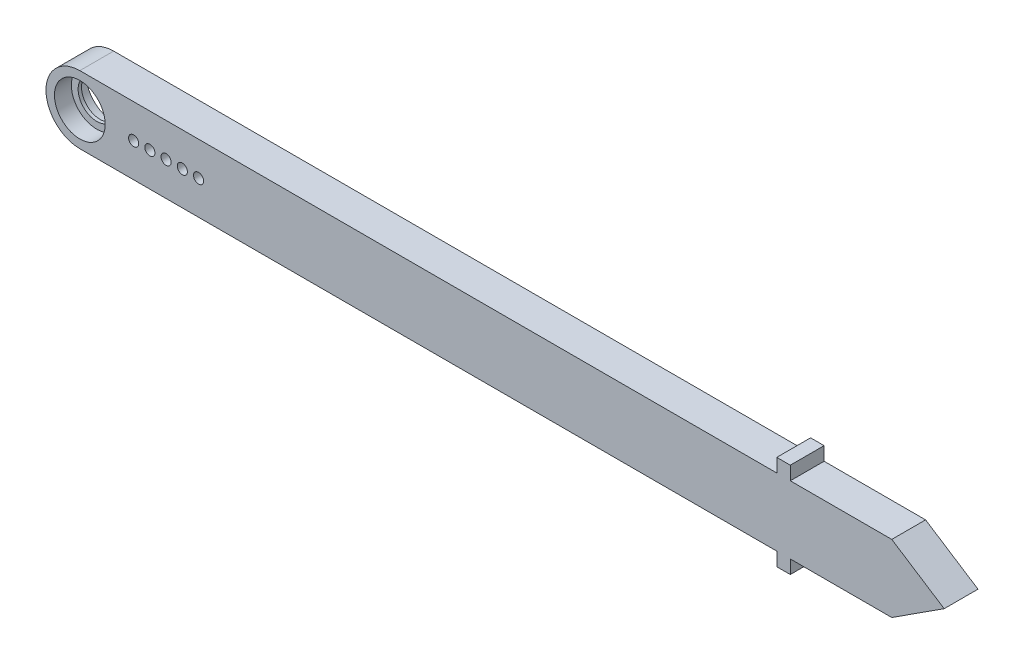
SolidWorks part; units mm, degrees
ref_plane "Front Plane" through (0, 0, 0) normal (0, 0, 1) x (1, 0, 0)
ref_plane "Top Plane" through (0, 0, 0) normal (0, 1, 0) x (1, 0, 0)
ref_plane "Right Plane" through (0, 0, 0) normal (1, 0, 0) x (0, 0, -1)
sketch "Sketch1" plane through (0, 0, 0) normal (0, 0, 1) x (1, 0, 0)
  line L0 (0, 0) -> (120, 0) construction
  line L1 (120, 5) -> (120, -5)
  line L2 (0, 5) -> (120, 5)
  line L3 (0, -5) -> (120, -5)
  circle A0 centre (0, 0) radius 3.75
  circle A1 centre (1.2272, 0) radius 0.1309
  arc A2 (0, 5) -> (0, -5) centre (0, 0) ccw
  dimension "D1" = 7.5
  dimension "D2" = 120
  dimension "D3" = 10
extrude "Boss-Extrude1" add sketch "Sketch1" along normal blind 5 contours L2 A2 L3 A0 region at (60.1767, 0, 0)
sketch "Sketch3" plane through (0, 0, 0) normal (0, 0, -1) x (-1, 0, 0)
  line L0 (-18.4, 0) -> (4.1, 0) construction
  line L3 (-16.1297, 2.7494) -> (0, 4.1)
  line L4 (-16.1297, -2.7494) -> (0, -4.1)
  arc A4 (0, -4.1) -> (0, 4.1) centre (0, 0) ccw
  arc A5 (-16.1297, 2.7494) -> (-16.1297, -2.7494) centre (-15.6, 0) ccw
  dimension "D2" = 8.2
  dimension "D3" = 5.6
  dimension "D1" = 22.5
extrude "Cut-Extrude2" cut sketch "Sketch3" against normal blind 2
sketch "Sketch4" plane through (0, 0, 2) normal (0, 0, -1) x (-1, 0, 0)
  circle A1 centre (0, 0) radius 2.75
  circle A2 centre (0, 0) radius 3.75
  dimension "D1" = 5.5
  dimension "D2" = 7.5
extrude "Boss-Extrude2" add sketch "Sketch4" against normal blind 0.5
sketch "Sketch5" plane through (0, 5, 0) normal (0, 1, 0) x (1, 0, 0)
  line L0 (105, 0) -> (105, -5)
  line L1 (0, 0) -> (120, 0) construction
  line L2 (0, -5) -> (120, -5) construction
  line L4 (103, 0) -> (103, -5)
  line L5 (103, -5) -> (105, -5)
  line L6 (103, 0) -> (105, 0)
  line L7 (120, -5) -> (120, 0) construction
  dimension "D1" = 15
  dimension "D2" = 2
extrude "Boss-Extrude3" add sketch "Sketch5" along normal blind 2
extrude "Boss-Extrude4" add sketch "Sketch5<2>" against normal blind 12
sketch "Sketch5<2>" plane through (0, 5, 0) normal (0, 1, 0) x (1, 0, 0) same geometry as "Sketch5"
sketch "Sketch6" plane through (0, 0, 2) normal (0, 0, -1) x (-1, 0, 0)
  line L0 (-2.75, 0) -> (-12, 0) construction
  line L1 (-12, 0) -> (-15.9, 0)
  line L2 (-18.3, 0) -> (-2.75, 0) construction
  circle A1 centre (0, 0) radius 2.75 construction
  circle A2 centre (-12.75, 0) radius 0.75
  circle A3 centre (-15.15, 0) radius 0.75
  circle A4 centre (-10.35, 0) radius 0.75
  circle A5 centre (-7.95, 0) radius 0.75
  circle A6 centre (-17.55, 0) radius 0.75
  dimension "D2" = 1.5
  dimension "D4" = 1.5
  dimension "D1" = 14.05
  dimension "D3" = 3.9
  dimension "D5" = 3
  dimension "D6" = 2
extrude "Cut-Extrude3" cut sketch "Sketch6" against normal through all and the other way through all contours A6 | L1 A3 | L1 A2 | A4 L0 | A5 L0 | L0 A5 | L0 A4 | L1 A2 | L1 A3 region at (15.15, -0.3183, 2) region at (12.75, 0.3183, 2) region at (12.75, -0.3183, 2) region at (15.15, 0.3183, 2) region at (10.35, 0, 2) region at (7.95, 0, 2) region at (17.55, 0, 2)
sketch "Sketch7" plane through (0, 0, 5) normal (0, 0, 1) x (1, 0, 0)
  line L0 (120, 5) -> (127.7432, 0)
  line L1 (127.7432, 0) -> (120, -5)
  line L2 (120, -5) -> (120, 5)
extrude "Boss-Extrude5" add sketch "Sketch7" against normal up to surface (5 mm away) up to face at (7.6074, 0, 0)
